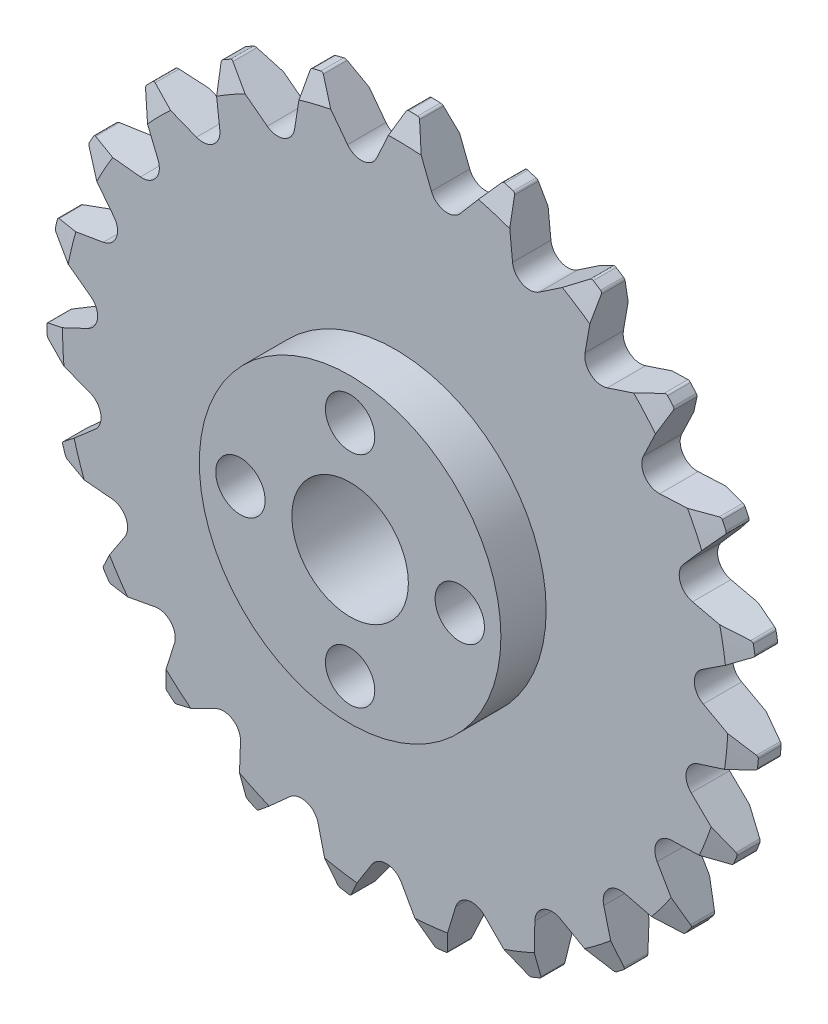
SolidWorks part; units mm, degrees
material "2024 Alloy"
ref_plane "Front Plane" through (0, 0, 0) normal (0, 0, 1) x (1, 0, 0)
ref_plane "Top Plane" through (0, 0, 0) normal (0, 1, 0) x (1, 0, 0)
ref_plane "Right Plane" through (0, 0, 0) normal (1, 0, 0) x (0, 0, -1)
sketch "Sketch1" plane through (0, 0, 0) normal (0, 1, 0) x (1, 0, 0)
  line L0 (26, 2.8) -> (0, 2.8)
  line L1 (0, 2.8) -> (0, 0)
  line L2 (0, 0) -> (26, 0)
  line L3 (26, 0) -> (26, 2.8)
  line L4 (0, 2.8) -> (0, 0) construction
revolve "Revolve1" add sketch "Sketch1" angle 360 about L4 reverse direction yes
sketch "Sketch2" plane through (0, 0, -2.8) normal (0, 0, -1) x (-1, 0, 0)
  line L0 (18.8013, 17.9586) -> (17.3085, 14.3114)
  line L1 (18.595, 12.5946) -> (22.5146, 13.0035)
  arc A0 (22.5146, 13.0035) -> (18.8013, 17.9586) centre (0, 0) ccw
  arc A1 (17.3085, 14.3114) -> (18.595, 12.5946) centre (18.4653, 13.8379) ccw
extrude "Cut-Extrude1" cut sketch "Sketch2" against normal through all
sketch "Sketch3" plane through (0, 0, -2.8) normal (0, 0, -1) x (-1, 0, 0)
  line L0 (22.9493, 12.2201) -> (20.5278, 9.1109)
  line L1 (21.3035, 7.1107) -> (25.188, 6.4469)
  arc A0 (25.188, 6.4469) -> (22.9493, 12.2201) centre (0, 0) ccw
  arc A1 (20.5278, 9.1109) -> (21.3035, 7.1107) centre (21.514, 8.3429) ccw
extrude "Cut-Extrude2" cut sketch "Sketch3" against normal through all
sketch "Sketch4" plane through (0, 0, -2.8) normal (0, 0, -1) x (-1, 0, 0)
  line L0 (25.3952, 5.5753) -> (22.2247, 3.2347)
  line L1 (22.4319, 1.0994) -> (25.9934, -0.5878)
  arc A0 (25.9934, -0.5878) -> (25.3952, 5.5753) centre (0, 0) ccw
  arc A1 (22.2247, 3.2347) -> (22.4319, 1.0994) centre (22.9671, 2.2291) ccw
extrude "Cut-Extrude3" cut sketch "Sketch4" against normal through all
sketch "Sketch5" plane through (0, 0, -2.8) normal (0, 0, -1) x (-1, 0, 0)
  line L0 (25.9577, -1.483) -> (22.2732, -2.8814)
  line L1 (21.8967, -4.9934) -> (24.8709, -7.5789)
  arc A0 (24.8709, -7.5789) -> (25.9577, -1.483) centre (0, 0) ccw
  arc A1 (22.2732, -2.8814) -> (21.8967, -4.9934) centre (22.7168, -4.05) ccw
extrude "Cut-Extrude4" cut sketch "Sketch5" against normal through all
sketch "Sketch6" plane through (0, 0, -2.8) normal (0, 0, -1) x (-1, 0, 0)
  line L0 (24.595, -8.4313) -> (20.6699, -8.7838)
  line L1 (19.7375, -10.7159) -> (21.9038, -14.0079)
  arc A0 (21.9038, -14.0079) -> (24.595, -8.4313) centre (0, 0) ccw
  arc A1 (20.6699, -8.7838) -> (19.7375, -10.7159) centre (20.7817, -10.0288) ccw
extrude "Cut-Extrude5" cut sketch "Sketch6" against normal through all
sketch "Sketch7" plane through (0, 0, -2.8) normal (0, 0, -1) x (-1, 0, 0)
  line L0 (21.4082, -14.7543) -> (17.5336, -14.0347)
  line L1 (16.1145, -15.6436) -> (17.3123, -19.3981)
  arc A0 (17.3123, -19.3981) -> (21.4082, -14.7543) centre (0, 0) ccw
  arc A1 (17.5336, -14.0347) -> (16.1145, -15.6436) centre (17.3053, -15.2637) ccw
extrude "Cut-Extrude6" cut sketch "Sketch7" against normal through all
sketch "Sketch8" plane through (0, 0, -2.8) normal (0, 0, -1) x (-1, 0, 0)
  line L0 (16.6337, -19.983) -> (13.0969, -18.2448)
  line L1 (11.2963, -19.4112) -> (11.4367, -23.3495)
  arc A0 (11.4367, -23.3495) -> (16.6337, -19.983) centre (0, 0) ccw
  arc A1 (13.0969, -18.2448) -> (11.2963, -19.4112) centre (12.5455, -19.3666) ccw
extrude "Cut-Extrude7" cut sketch "Sketch8" against normal through all
sketch "Sketch9" plane through (0, 0, -2.8) normal (0, 0, -1) x (-1, 0, 0)
  line L0 (10.6255, -23.7297) -> (7.6888, -21.1017)
  line L1 (5.6403, -21.7391) -> (4.713, -25.5693)
  arc A0 (4.713, -25.5693) -> (10.6255, -23.7297) centre (0, 0) ccw
  arc A1 (7.6888, -21.1017) -> (5.6403, -21.7391) centre (6.8552, -22.0332) ccw
extrude "Cut-Extrude8" cut sketch "Sketch9" against normal through all
sketch "Sketch10" plane through (0, 0, -2.8) normal (0, 0, -1) x (-1, 0, 0)
  line L0 (3.8293, -25.7165) -> (1.7105, -22.3936)
  line L1 (-0.4339, -22.4547) -> (-2.3603, -25.8926)
  arc A0 (-2.3603, -25.8926) -> (3.8293, -25.7165) centre (0, 0) ccw
  arc A1 (1.7105, -22.3936) -> (-0.4339, -22.4547) centre (0.6565, -23.0657) ccw
extrude "Cut-Extrude9" cut sketch "Sketch10" against normal through all
sketch "Sketch11" plane through (0, 0, -2.8) normal (0, 0, -1) x (-1, 0, 0)
  line L0 (-3.2509, -25.796) -> (-4.3946, -22.0247)
  line L1 (-6.476, -21.5049) -> (-9.2585, -24.2957)
  arc A0 (-9.2585, -24.2957) -> (-3.2509, -25.796) centre (0, 0) ccw
  arc A1 (-4.3946, -22.0247) -> (-6.476, -21.5049) centre (-5.5908, -22.3875) ccw
extrude "Cut-Extrude10" cut sketch "Sketch11" against normal through all
sketch "Sketch12" plane through (0, 0, -2.8) normal (0, 0, -1) x (-1, 0, 0)
  line L0 (-10.0901, -23.9623) -> (-10.1739, -20.0223)
  line L1 (-12.0379, -18.9602) -> (-15.4701, -20.8968)
  arc A0 (-15.4701, -20.8968) -> (-10.0901, -23.9623) centre (0, 0) ccw
  arc A1 (-10.1739, -20.0223) -> (-12.0379, -18.9602) centre (-11.4236, -20.0489) ccw
extrude "Cut-Extrude11" cut sketch "Sketch12" against normal through all
sketch "Sketch13" plane through (0, 0, -2.8) normal (0, 0, -1) x (-1, 0, 0)
  line L0 (-16.1808, -20.3514) -> (-15.1985, -16.5349)
  line L1 (-16.7069, -15.0093) -> (-20.5343, -15.9481)
  arc A0 (-20.5343, -15.9481) -> (-16.1808, -20.3514) centre (0, 0) ccw
  arc A1 (-15.1985, -16.5349) -> (-16.7069, -15.0093) centre (-16.4091, -16.2234) ccw
extrude "Cut-Extrude12" cut sketch "Sketch13" against normal through all
sketch "Sketch14" plane through (0, 0, -2.8) normal (0, 0, -1) x (-1, 0, 0)
  line L0 (-21.0716, -15.2312) -> (-19.096, -11.8213)
  line L1 (-20.1368, -9.9453) -> (-24.0756, -9.8167)
  arc A0 (-24.0756, -9.8167) -> (-21.0716, -15.2312) centre (0, 0) ccw
  arc A1 (-19.096, -11.8213) -> (-20.1368, -9.9453) centre (-20.1776, -11.1946) ccw
extrude "Cut-Extrude13" cut sketch "Sketch14" against normal through all
sketch "Sketch15" plane through (0, 0, -2.8) normal (0, 0, -1) x (-1, 0, 0)
  line L0 (-24.3995, -8.9813) -> (-21.5772, -6.2309)
  line L1 (-22.0733, -4.1437) -> (-25.8313, -2.9571)
  arc A0 (-25.8313, -2.9571) -> (-24.3995, -8.9813) centre (0, 0) ccw
  arc A1 (-21.5772, -6.2309) -> (-22.0733, -4.1437) centre (-22.4496, -5.3357) ccw
extrude "Cut-Extrude14" cut sketch "Sketch15" against normal through all
sketch "Sketch16" plane through (0, 0, -2.8) normal (0, 0, -1) x (-1, 0, 0)
  line L0 (-25.9178, -2.0654) -> (-22.4581, -0.1783)
  line L1 (-22.3727, 1.9653) -> (-25.6712, 4.1217)
  arc A0 (-25.6712, 4.1217) -> (-25.9178, -2.0654) centre (0, 0) ccw
  arc A1 (-22.4581, -0.1783) -> (-22.3727, 1.9653) centre (-23.0567, 0.919) ccw
extrude "Cut-Extrude15" cut sketch "Sketch16" against normal through all
sketch "Sketch17" plane through (0, 0, -2.8) normal (0, 0, -1) x (-1, 0, 0)
  line L0 (-25.514, 5.0037) -> (-21.6734, 5.8874)
  line L1 (-21.0128, 7.9285) -> (-23.6072, 10.8949)
  arc A0 (-23.6072, 10.8949) -> (-25.514, 5.0037) centre (0, 0) ccw
  arc A1 (-21.6734, 5.8874) -> (-21.0128, 7.9285) centre (-21.9537, 7.1056) ccw
extrude "Cut-Extrude16" cut sketch "Sketch17" against normal through all
sketch "Sketch18" plane through (0, 0, -2.8) normal (0, 0, -1) x (-1, 0, 0)
  line L0 (-23.2178, 11.7018) -> (-19.2813, 11.5165)
  line L1 (-18.0945, 13.3037) -> (-19.7924, 16.86)
  arc A0 (-19.7924, 16.86) -> (-23.2178, 11.7018) centre (0, 0) ccw
  arc A1 (-19.2813, 11.5165) -> (-18.0945, 13.3037) centre (-19.2226, 12.7651) ccw
extrude "Cut-Extrude17" cut sketch "Sketch18" against normal through all
sketch "Sketch19" plane through (0, 0, -2.8) normal (0, 0, -1) x (-1, 0, 0)
  line L0 (-19.1998, 17.5319) -> (-15.4592, 16.2915)
  line L1 (-13.8342, 17.6922) -> (-14.5097, 21.5748)
  arc A0 (-14.5097, 21.5748) -> (-19.1998, 17.5319) centre (0, 0) ccw
  arc A1 (-15.4592, 16.2915) -> (-13.8342, 17.6922) centre (-15.0657, 17.478) ccw
extrude "Cut-Extrude18" cut sketch "Sketch19" against normal through all
sketch "Sketch20" plane through (0, 0, -2.8) normal (0, 0, -1) x (-1, 0, 0)
  line L0 (-13.7577, 22.0618) -> (-10.4905, 19.8582)
  line L1 (-8.5479, 20.7685) -> (-8.1508, 24.6894)
  arc A0 (-8.1508, 24.6894) -> (-13.7577, 22.0618) centre (0, 0) ccw
  arc A1 (-10.4905, 19.8582) -> (-8.5479, 20.7685) centre (-9.7916, 20.8945) ccw
extrude "Cut-Extrude19" cut sketch "Sketch20" against normal through all
sketch "Sketch21" plane through (0, 0, -2.8) normal (0, 0, -1) x (-1, 0, 0)
  line L0 (-7.2953, 24.9555) -> (-4.7438, 21.9521)
  line L1 (-2.6277, 22.3046) -> (-1.1874, 25.9729)
  arc A0 (-1.1874, 25.9729) -> (-7.2953, 24.9555) centre (0, 0) ccw
  arc A1 (-4.7438, 21.9521) -> (-2.6277, 22.3046) centre (-3.7912, 22.7614) ccw
extrude "Cut-Extrude20" cut sketch "Sketch21" against normal through all
sketch "Sketch22" plane through (0, 0, -2.8) normal (0, 0, -1) x (-1, 0, 0)
  line L0 (-0.2919, 25.9984) -> (1.3547, 22.418)
  line L1 (3.4875, 22.1864) -> (5.864, 25.3301)
  arc A0 (5.864, 25.3301) -> (-0.2919, 25.9984) centre (0, 0) ccw
  arc A1 (1.3547, 22.418) -> (3.4875, 22.1864) centre (2.4903, 22.9402) ccw
extrude "Cut-Extrude21" cut sketch "Sketch22" against normal through all
sketch "Sketch23" plane through (0, 0, -2.8) normal (0, 0, -1) x (-1, 0, 0)
  line L0 (6.7332, 25.113) -> (7.3527, 21.2211)
  line L1 (9.344, 20.4228) -> (12.4805, 22.8087)
  arc A0 (12.4805, 22.8087) -> (6.7332, 25.113) centre (0, 0) ccw
  arc A1 (7.3527, 21.2211) -> (9.344, 20.4228) centre (8.5872, 21.4176) ccw
extrude "Cut-Extrude22" cut sketch "Sketch23" against normal through all
sketch "Sketch24" plane through (0, 0, -2.8) normal (0, 0, -1) x (-1, 0, 0)
  line L0 (13.2589, 22.3652) -> (12.8055, 18.4505)
  line L1 (14.5075, 17.1445) -> (18.1714, 18.5957)
  arc A0 (18.1714, 18.5957) -> (13.2589, 22.3652) centre (0, 0) ccw
  arc A1 (12.8055, 18.4505) -> (14.5075, 17.1445) centre (14.0472, 18.3066) ccw
extrude "Cut-Extrude23" cut sketch "Sketch24" against normal through all
sketch "Sketch25" plane through (0, 0, 0) normal (0, 1, 0) x (1, 0, 0)
  line L0 (11, 0) -> (0, 0)
  line L1 (0, 0) -> (0, -3.302)
  line L2 (0, -3.302) -> (11, -3.302)
  line L3 (11, -3.302) -> (11, 0)
  line L4 (0, 0) -> (0, -3.302) construction
revolve "Revolve2" add sketch "Sketch25" angle 360 about L4 reverse direction yes
hole_wizard "Ø8.0 (8) Diameter Hole1" positions "Sketch27" profile "Sketch26" hole size "Ø8.0" standard "ANSI Metric"
sketch "Sketch27" plane through (0, 0, 3.302) normal (0, 0, 1) x (1, 0, 0)
  point P0 (0, 0)
sketch "Sketch26" plane through (0, 0, 3.302) normal (1, 0, 0) x (0, -1, 0)
  line L0 (0, 0) -> (0, 6.102)
  line L1 (0, 6.102) -> (4.25, 6.102)
  line L2 (4.25, 6.102) -> (4.25, 0)
  line L5 (4.25, 0) -> (0, 0)
  line L11 (0, -6.35) -> (0, 107.95) construction
  dimension "Thru Hole Dia." = 8.5
  dimension "Thru Hole Depth" = 6.102
hole_wizard "Ø3.6 (3.6) Diameter Hole1" positions "Sketch29" profile "Sketch28" hole size "Ø3.6" standard "ANSI Metric"
sketch "Sketch29" plane through (0, 0, 3.302) normal (0, 0, 1) x (1, 0, 0)
  point P0 (0, 8)
  point P1 (-8, 0)
  point P2 (0, -8)
sketch "Sketch28" plane through (0, 8, 3.302) normal (1, 0, 0) x (0, -1, 0)
  line L0 (0, 0) -> (0, 6.102)
  line L1 (0, 6.102) -> (1.8, 6.102)
  line L2 (1.8, 6.102) -> (1.8, 0)
  line L5 (1.8, 0) -> (0, 0)
  line L11 (0, -6.35) -> (0, 107.95) construction
  dimension "Thru Hole Dia." = 3.6
  dimension "Thru Hole Depth" = 6.102
hole_wizard "Ø3.6 (3.6) Diameter Hole2" positions "Sketch31" profile "Sketch30" hole size "Ø3.6" standard "ANSI Metric"
sketch "Sketch31" plane through (0, 0, -2.8) normal (0, 0, -1) x (-1, 0, 0)
  point P0 (-8, 0)
sketch "Sketch30" plane through (8, 0, -2.8) normal (1, 0, 0) x (0, 1, 0)
  line L0 (0, 0) -> (0, 6.102)
  line L1 (0, 6.102) -> (1.8, 6.102)
  line L2 (1.8, 6.102) -> (1.8, 0)
  line L5 (1.8, 0) -> (0, 0)
  line L11 (0, -6.35) -> (0, 107.95) construction
  dimension "Thru Hole Dia." = 3.6
  dimension "Thru Hole Depth" = 6.102
fillet "Fillet1" radius 0.2 46 edges at (25.8313, -2.9571, -1.4) (25.9178, -2.0654, -1.4) (9.2585, -24.2957, -1.4) (10.0901, -23.9623, -1.4) (14.5097, 21.5748, -1.4) (13.7577, 22.0618, -1.4) (-13.2589, 22.3652, -1.4) (-12.4805, 22.8087, -1.4) (20.5343, -15.9481, -1.4) (21.0716, -15.2312, -1.4) (-18.8013, 17.9586, -1.4) (-18.1714, 18.5957, -1.4) (23.6072, 10.8949, -1.4) (23.2178, 11.7018, -1.4) (1.1874, 25.9729, -1.4) (0.2919, 25.9984, -1.4) (-22.9493, 12.2201, -1.4) (-22.5146, 13.0035, -1.4) (15.4701, -20.8968, -1.4) (16.1808, -20.3514, -1.4) (24.0756, -9.8167, -1.4) (24.3995, -8.9813, -1.4) (-25.3952, 5.5753, -1.4) (-25.188, 6.4469, -1.4) (25.6712, 4.1217, -1.4) (25.514, 5.0037, -1.4) (19.7924, 16.86, -1.4) (19.1998, 17.5319, -1.4) (-25.9577, -1.483, -1.4) (-25.9934, -0.5878, -1.4) (8.1508, 24.6894, -1.4) (7.2953, 24.9555, -1.4) (-5.864, 25.3301, -1.4) (-6.7332, 25.113, -1.4) (-24.595, -8.4313, -1.4) (-24.8709, -7.5789, -1.4) (-21.4082, -14.7543, -1.4) (-21.9038, -14.0079, -1.4) (-16.6337, -19.983, -1.4) (-17.3123, -19.3981, -1.4) (-10.6255, -23.7297, -1.4) (-11.4367, -23.3495, -1.4) (-3.8293, -25.7165, -1.4) (-4.713, -25.5693, -1.4) (3.2509, -25.796, -1.4) (2.3603, -25.8926, -1.4)
sketch "Sketch32" plane through (0, 0, 0) normal (1, 0, 0) x (0, 0, -1)
  line L0 (0, 24.2697) -> (0, 26.0477)
  line L1 (0, 26.0477) -> (0.5842, 26.0477)
  line L2 (0.5842, 26.0477) -> (0, 24.2697)
  line L3 (1.4, 25.8518) -> (1.4, 8.3868) construction
  line L4 (2.8, 25.8518) -> (0, 25.8518) construction
  line L5 (0, 0) -> (13.057, 0) construction
  line L6 (2.2158, 26.0477) -> (2.8, 24.2697)
  line L7 (2.8, 26.0477) -> (2.2158, 26.0477)
  line L8 (2.8, 24.2697) -> (2.8, 26.0477)
  dimension "D1" = 24.2697
  dimension "D2" = 1.778
  dimension "D3" = 0.5842
revolve "Cut-Revolve1" cut sketch "Sketch32" angle 360 about L5
